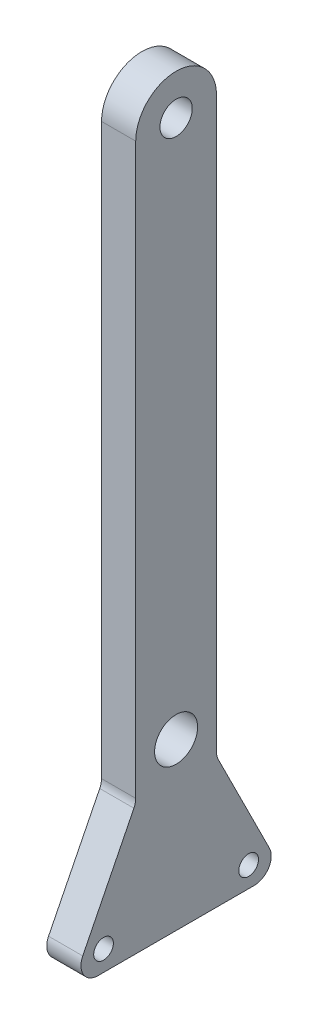
SolidWorks part; units mm, degrees
ref_plane "Front Plane" through (0, 0, 0) normal (0, 0, 1) x (1, 0, 0)
ref_plane "Top Plane" through (0, 0, 0) normal (0, 1, 0) x (1, 0, 0)
ref_plane "Right Plane" through (0, 0, 0) normal (1, 0, 0) x (0, 0, -1)
sketch "Sketch1" plane through (0, 0, 0) normal (1, 0, 0) x (0, 0, -1)
  line L0 (-13.4747, 0) -> (13.4747, 0) construction
  line L1 (0, 0) -> (0, 26.9494) construction
  line L2 (-13.4747, 0) -> (0, 26.9494) construction
  line L3 (0, 26.9494) -> (13.4747, 0) construction
  line L4 (13.4747, 0) -> (-13.4747, 0) construction
  line L5 (19.6394, -3.81) -> (-19.6394, -3.81)
  line L6 (-19.6394, -3.81) -> (0, 35.4688)
  line L7 (0, 35.4688) -> (19.6394, -3.81)
  line L8 (0, 26.9494) -> (0, 126.9494) construction
  line L9 (0, 26.9494) -> (0, 126.9494) construction
  line L12 (-7.5, 26.9494) -> (-7.5, 126.9494)
  line L13 (7.5, 26.9494) -> (7.5, 126.9494)
  line L14 (-7.5, 26.9494) -> (-7.5, 20.4688)
  line L15 (7.5, 26.9494) -> (7.5, 20.4688)
  circle A0 centre (-13.4747, 0) radius 1.8288
  circle A1 centre (0, 26.9494) radius 4
  circle A2 centre (13.4747, 0) radius 1.8288
  circle A3 centre (0, 126.9494) radius 3
  arc A6 (-7.5, 26.9494) -> (7.5, 26.9494) centre (0, 26.9494) ccw
  arc A7 (7.5, 126.9494) -> (-7.5, 126.9494) centre (0, 126.9494) ccw
  point P4 (0, 0)
  point P14 (0, 76.9494)
  dimension "D3" = 3.6576
  dimension "D4" = 8
  dimension "D7" = 6
  dimension "D1" = 26.9494
  dimension "D5" = 100
  dimension "D6" = 15
  dimension "D2" = 3.81
extrude "Boss-Extrude1" add sketch "Sketch1" along normal blind 6.35 contours A6 L6 L5 L7 A2 A0 | L6 A6 L7 A1 | L13 A7 L12 A6 L6 A1 L7 A3 | A1 L7 L6 | A6 L7 L15 | A6 L14 L6 region at (0, 6.8071, 0) region at (0, 23.0136, -7.1228) region at (0, 23.0136, 7.1228) region at (0, 22.4682, 0) region at (0, 79.7176, 0) region at (0, 32.2331, 0)
fillet "Fillet1" radius 3.175 4 edges at (3.175, -3.81, -19.6394) (3.175, -3.81, 19.6394) (3.175, 20.4688, -7.5) (3.175, 20.4688, 7.5)
